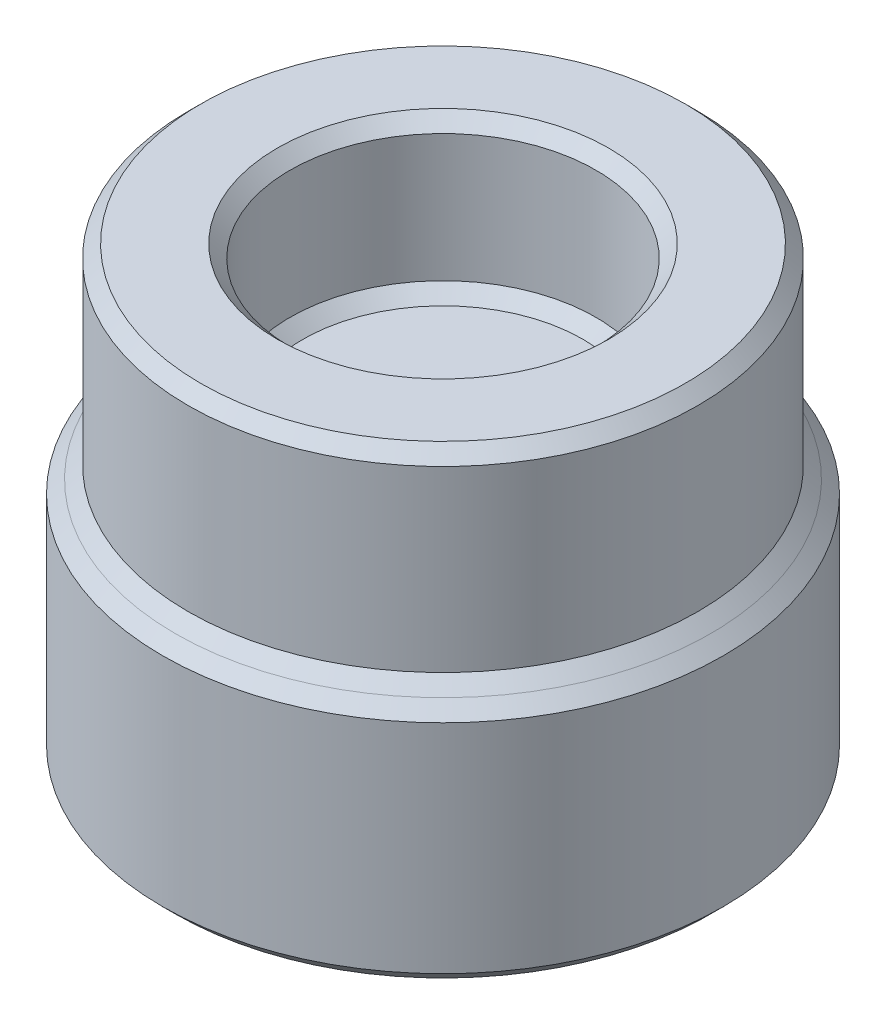
SolidWorks part; units mm, degrees
note: '?' marks a value the reader was unsure of. The reader was unsure of these and kept them because the rebuilt part matched: shared geometry of "Sketch1<3>".
material "ABS"
ref_plane "Front Plane" through (0, 0, 0) normal (0, 0, 1) x (1, 0, 0)
ref_plane "Top Plane" through (0, 0, 0) normal (0, 1, 0) x (1, 0, 0)
ref_plane "Right Plane" through (0, 0, 0) normal (1, 0, 0) x (0, 0, -1)
ref_axis "X Axis" through (88.99, 0, 0) along (-1, 0, 0)?
ref_axis "Y Axis" through (0, 55, 0) along (0, -1, 0)?
ref_axis "Z Axis" through (0, 0, -88.99) along (0, 0, 1)?
sketch "Sketch1" plane through (0, 0, 0) normal (0, 1, 0) x (1, 0, 0)
  circle A0 centre (0, 0) radius 5
  circle A1 centre (0, 0) radius 3
  dimension "D1" = 6
  dimension "D2" = 10
extrude "Boss-Extrude1" add sketch "Sketch1" along normal blind 1 contours A1 | A0 A1
extrude "Boss-Extrude2" add sketch "Sketch1<3>" along normal blind 4
sketch "Sketch1<3>" plane through (0, 0, 0) normal (0, 1, 0) x (1, 0, 0) same geometry as "Sketch1"
chamfer "Chamfer1" distance 0.25 angle 45 3 edges at (0, 4, 3) (0, 4, 5) (0, 1, 3)
sketch "Sketch5" plane through (0, 0, 0) normal (0, 1, 0) x (1, 0, 0)
  circle A0 centre (0, 0) radius 5.5
  dimension "D1" = 11
extrude "Boss-Extrude4" add sketch "Sketch5" against normal blind 4.7625
sketch "Sketch4" plane through (0, -4.7625, 0) normal (0, -1, 0) x (-1, 0, 0)
  point P0 (0, 0)
hole_wizard "3/8 (0.375) Diameter Hole1" [suppressed] positions "Sketch4" profile "Sketch3" hole size "3/8" standard "ANSI Inch"
sketch "Sketch3" plane through (0, -12.5, 0) normal (1, 0, 0) x (0, 0, -1)
  line L0 (0, 0) -> (0, 12.5)
  line L1 (0, 12.5) -> (4.7625, 12.0833)
  line L2 (4.7625, 12.0833) -> (4.7625, 0.635)
  line L3 (4.7625, 0.635) -> (5.3975, 0)
  line L5 (5.3975, 0) -> (0, 0)
  line L6 (-4.7625, 0.635) -> (-5.3975, 0) construction
  line L10 (0, 12.5) -> (-4.7625, 12.0833) construction
  line L11 (0, -6.35) -> (0, 107.95) construction
  dimension "Hole Dia." = 9.525
  dimension "Hole Depth" = 12.5
  dimension "Near C'Sink Dia." = 10.795
  dimension "Near C'Sink Angle" = 90
  dimension "Drill Angle" = 170
sketch "Sketch8" plane through (0, -4.7625, 0) normal (0, -1, 0) x (-1, 0, 0)
  point P0 (0, 0)
hole_wizard "#2 (0.221) Diameter Hole1" positions "Sketch8" profile "Sketch7" hole size "#2" standard "ANSI Inch"
sketch "Sketch7" plane through (0, -4.7625, 0) normal (1, 0, 0) x (0, 0, -1)
  line L0 (0, 0) -> (0, 4.76)
  line L1 (0, 4.76) -> (2.8067, 4.2651)
  line L2 (2.8067, 4.2651) -> (2.8067, 0.635)
  line L3 (2.8067, 0.635) -> (3.4417, 0)
  line L5 (3.4417, 0) -> (0, 0)
  line L6 (-2.8067, 0.635) -> (-3.4417, 0) construction
  line L10 (0, 4.76) -> (-2.8067, 4.2651) construction
  line L11 (0, -6.35) -> (0, 107.95) construction
  dimension "Hole Dia." = 5.6134
  dimension "Hole Depth" = 4.76
  dimension "Near C'Sink Dia." = 6.8834
  dimension "Near C'Sink Angle" = 90
  dimension "Drill Angle" = 160
sketch "Sketch11" [suppressed] plane through (0, -2.75, 0) normal (0, -1, 0) x (-1, 0, 0)
  point P0 (0, 0)
hole_wizard "Ø6.0 (6) Diameter Hole1" [suppressed] positions "Sketch11" profile "Sketch10" hole size "Ø6.0" standard "ANSI Metric"
sketch "Sketch10" plane through (0, -2.75, 0) normal (1, 0, 0) x (0, 0, -1)
  line L0 (0, 0) -> (0, 3)
  line L1 (0, 3) -> (3, 3)
  line L2 (3, 3) -> (3, 0.125)
  line L3 (3, 0.125) -> (3.125, 0)
  line L5 (3.125, 0) -> (0, 0)
  line L6 (-3, 0.125) -> (-3.125, 0) construction
  line L10 (0, 3) -> (-3, 3) construction
  line L11 (0, -6.35) -> (0, 107.95) construction
  dimension "Hole Dia." = 6
  dimension "Hole Depth" = 3
  dimension "Near C'Sink Dia." = 6.25
  dimension "Near C'Sink Angle" = 90
  dimension "Drill Angle" = 180
chamfer "Chamfer2" distance 0.25 angle 45 2 edges at (0, -4.7625, 5.5) (0, 0, 5.5)
chamfer "Chamfer3" distance 0.25 angle 45 1 edges at (0, 0, 5)
